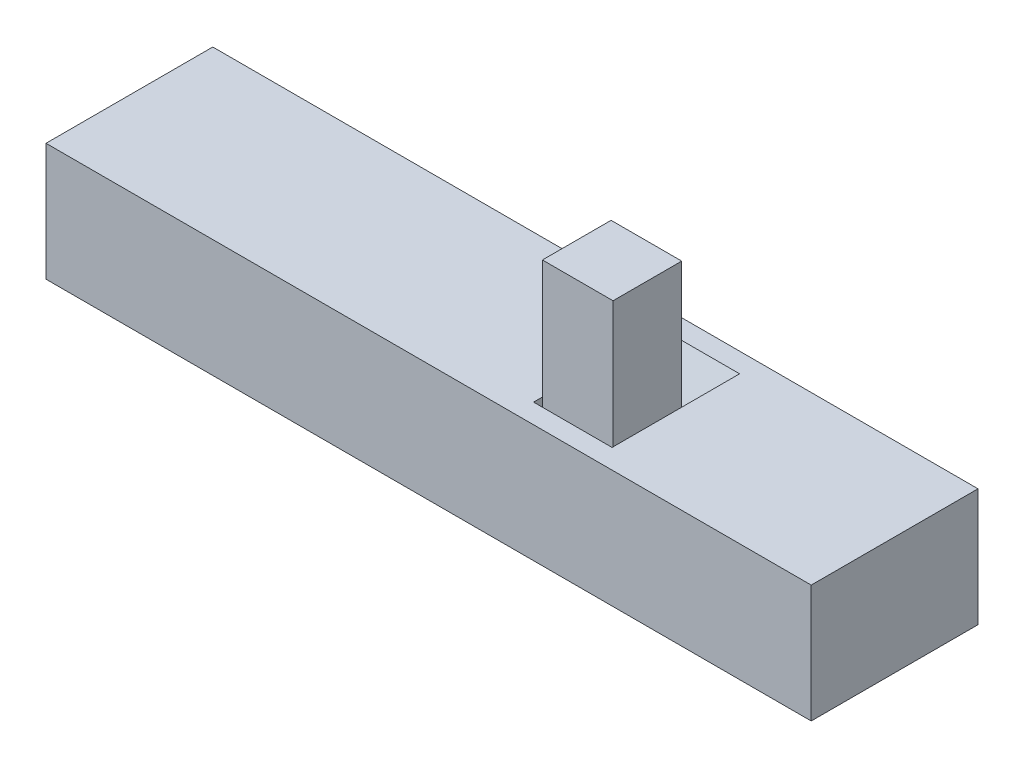
SolidWorks part; units mm, degrees
ref_plane "Front Plane" through (0, 0, 0) normal (0, 0, 1) x (1, 0, 0)
ref_plane "Top Plane" through (0, 0, 0) normal (0, 1, 0) x (1, 0, 0)
ref_plane "Right Plane" through (0, 0, 0) normal (1, 0, 0) x (0, 0, -1)
sketch "Sketch1" plane through (0, 0, 0) normal (0, 1, 0) x (1, 0, 0)
  line L1 (0, 0) -> (39, 0)
  line L2 (0, 0) -> (0, 8.5)
  line L3 (0, 8.5) -> (39, 8.5)
  line L4 (39, 0) -> (39, 8.5)
  dimension "D1" = 39
  dimension "D2" = 8.5
extrude "Boss-Extrude1" add sketch "Sketch1" along normal blind 6
sketch "Sketch2" plane through (0, 6, 0) normal (0, 1, 0) x (1, 0, 0)
  line L0 (0, 0) -> (39, 0) construction
  line L1 (23.85, 5) -> (27.85, 5)
  line L2 (23.85, 5) -> (23.85, 1)
  line L3 (23.85, 1) -> (27.85, 1)
  line L4 (27.85, 5) -> (27.85, 1)
  line L6 (0, 8.5) -> (0, 0) construction
  dimension "D1" = 4
  dimension "D2" = 1
  dimension "D3" = 23.85
  dimension "D4" = 4
extrude "Cut-Extrude1" cut sketch "Sketch2" against normal blind 5
sketch "Sketch3" plane through (27.85, 0, 0) normal (-1, 0, 0) x (0, 0, 1)
  line L1 (-1, 1) -> (-5, 1)
  line L2 (-1, 1) -> (-1, 6)
  line L3 (-1, 6) -> (-5, 6)
  line L4 (-5, 1) -> (-5, 6)
  circle A0 centre (-3, 3.5) radius 1.5
  point P9 (-1, 3.5)
  point P11 (-3, 6)
  dimension "D1" = 3
extrude "Cut-Extrude2" cut sketch "Sketch3" against normal blind 4 and the other way blind 8 contours A0 region at (27.85, 3.5, -3)
sketch "Sketch4" plane through (27.85, 0, 0) normal (-1, 0, 0) x (0, 0, 1)
  line L0 (-4.75, 5.25) -> (-4.75, 12.25)
  line L1 (-4.75, 5.25) -> (-1.25, 5.25)
  line L2 (-4.75, 5.25) -> (-4.75, 1.75)
  line L3 (-4.75, 1.75) -> (-3, 1.75)
  line L4 (-1.25, 5.25) -> (-1.25, 3.5)
  line L5 (-4.75, 5.25) -> (-1.25, 1.75) construction
  line L6 (-4.75, 1.75) -> (-1.25, 5.25) construction
  line L7 (-4.75, 12.25) -> (-1.25, 12.25)
  line L8 (-1.25, 12.25) -> (-1.25, 5.25)
  circle A0 centre (-3, 3.5) radius 1.3
  arc A1 (-3, 1.75) -> (-1.25, 3.5) centre (-3, 3.5) ccw
  circle M8 centre (-3, 3.5) radius 1.5
  line M9 (-1, 6) -> (-5, 6)
  dimension "D1" = 2.6
  dimension "D5" = 1.75
  dimension "D2" = 3.5
  dimension "D3" = 3.5
  dimension "D4" = 7
extrude "Boss-Extrude2" add sketch "Sketch4" along normal blind 3.6 from offset 0.2 separate body contours L8 L7 L0 M9 | L8 L0 L1 M9 | L3 A1 L4 L1 L2 M8 | A0 | A0 M8 region at (27.85, 5.625, -3) region at (27.85, 5.2005, -3) region at (27.85, 9.125, -3) region at (27.85, 3.5, -3) region at (27.85, 3.5, -4.4576)
extrude "Boss-Extrude3" add sketch "Sketch4<3>" along normal blind 7.6 and the other way blind 3.6 contours A0
sketch "Sketch4<3>" plane through (27.85, 0, 0) normal (-1, 0, 0) x (0, 0, 1) same geometry as "Sketch4"
fillet "Fillet1" radius 1.75 1 edges at (25.85, 1.75, -4.75)
sketch "Sketch5" plane through (27.85, 0, 0) normal (-1, 0, 0) x (0, 0, 1)
  line L0 (-5, 6) -> (-7.5, 6)
  line L1 (-7.5, 6) -> (-5, 1)
  line L2 (-5, 1) -> (-5, 6)
  line L3 (-8.5, 6) -> (-8.5, 0) construction
  dimension "D1" = 1
extrude "Cut-Extrude3" cut sketch "Sketch5" along normal blind 4
